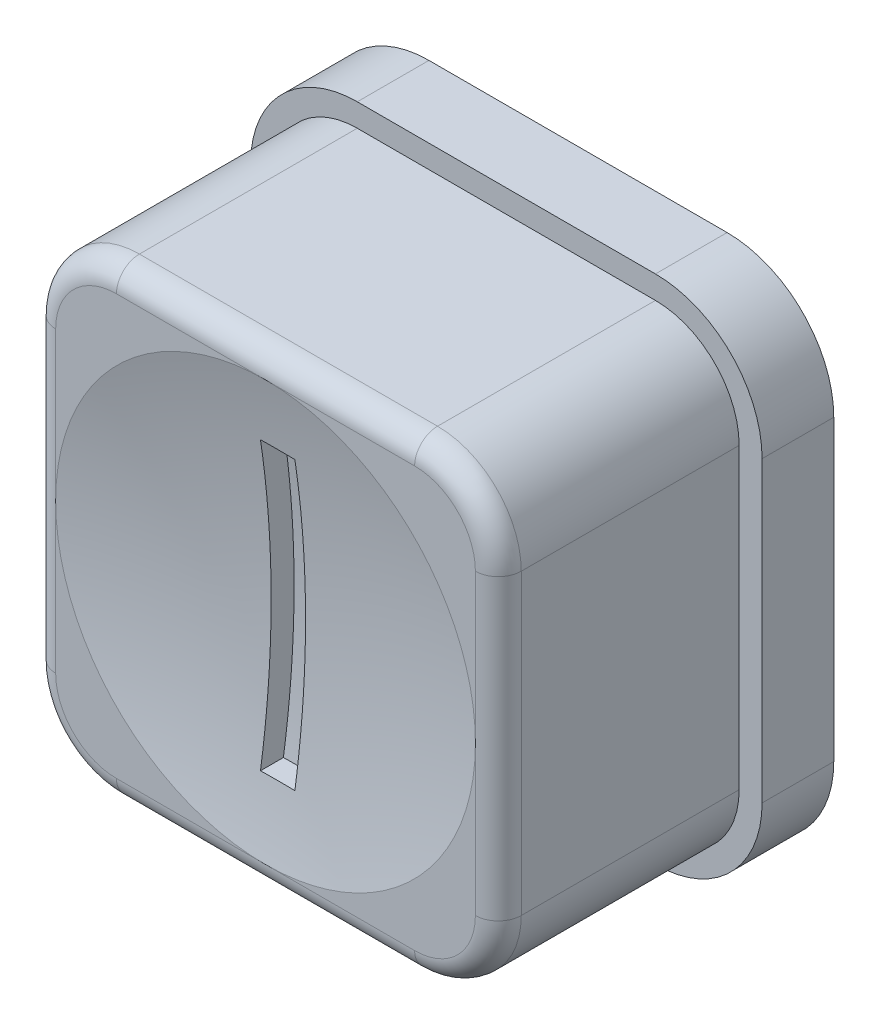
SolidWorks part; units mm, degrees
material "PET"
ref_plane "Front Plane" through (0, 0, 0) normal (0, 0, 1) x (1, 0, 0)
ref_plane "Top Plane" through (0, 0, 0) normal (0, 1, 0) x (1, 0, 0)
ref_plane "Right Plane" through (0, 0, 0) normal (1, 0, 0) x (0, 0, -1)
sketch "Sketch1" plane through (0, 0, 0) normal (0, 0, 1) x (1, 0, 0)
  line L0 (0, 0) -> (-5.1562, 0) construction
  line L4 (0, 5.1562) -> (0, -5.1562) construction
  line L8 (3.302, 5.1562) -> (-3.302, 5.1562)
  line L9 (-5.1562, 3.302) -> (-5.1562, -3.302)
  line L10 (-3.302, -5.1562) -> (3.302, -5.1562)
  line L11 (5.1562, -3.302) -> (5.1562, 3.302)
  arc A8 (-3.302, 5.1562) -> (-5.1562, 3.302) centre (-3.302, 3.302) ccw
  arc A9 (-5.1562, -3.302) -> (-3.302, -5.1562) centre (-3.302, -3.302) ccw
  arc A10 (3.302, -5.1562) -> (5.1562, -3.302) centre (3.302, -3.302) ccw
  arc A11 (5.1562, 3.302) -> (3.302, 5.1562) centre (3.302, 3.302) ccw
  point P6 (0, 0)
  dimension "D3" = 1.8542
  dimension "D4" = 10.3124
  dimension "D1" = 10.3124
  dimension "D5" = 10.3124
extrude "Boss-Extrude1" add sketch "Sketch1" against normal blind 5.334
fillet "Fillet1" radius 0.508 8 edges at (5.1562, 0, 0) (4.6131, -4.6131, 0) (0, -5.1562, 0) (-4.6131, -4.6131, 0) (-5.1562, 0, 0) (-4.6131, 4.6131, 0) (0, 5.1562, 0) (4.6131, 4.6131, 0)
sketch "Sketch2" plane through (0, 0, 0) normal (0, 0, 1) x (1, 0, 0)
  line L0 (0, 0) -> (0, -5.1562) construction
  line L1 (3.302, -5.1562) -> (-3.302, -5.1562) construction
  line L2 (0, 0) -> (5.1562, 0) construction
  line L3 (5.1562, 3.302) -> (5.1562, -3.302) construction
  circle A0 centre (0, 0) radius 4.572
  dimension "D1" = 9.144
extrude "Cut-Extrude1" [suppressed] cut sketch "Sketch2" against normal blind 0.254
sketch "Sketch3" [suppressed] plane through (0, 0, -0.254) normal (0, 0, 1) x (1, 0, 0)
  line L0 (0, -4.572) -> (0, 4.572) construction
  line L1 (-0.254, -4.572) -> (-0.254, 4.572)
  line L2 (0.254, -4.572) -> (0.254, 4.572)
  line L3 (0.254, -4.572) -> (0.254, 4.572)
  circle A0 centre (0, 0) radius 4.572 construction
  circle A1 centre (0, 0) radius 4.572 construction
  arc A2 (-0.254, -4.5649) -> (0.254, -4.5649) centre (0, 0) ccw
  arc A3 (0.254, 4.5649) -> (-0.254, 4.5649) centre (0, 0) ccw
  point P9 (0, 0)
  dimension "D2" = 0.254
  dimension "D1" = 0.254
extrude "Cut-Extrude2" [suppressed] cut sketch "Sketch3" against normal blind 0.127
sketch "Sketch4" plane through (0, 0, -5.334) normal (0, 0, -1) x (-1, 0, 0)
  line L8 (-5.6642, 3.302) -> (-5.6642, -3.302)
  line L9 (-3.302, -5.6642) -> (3.302, -5.6642)
  line L10 (5.6642, -3.302) -> (5.6642, 3.302)
  line L11 (3.302, 5.6642) -> (-3.302, 5.6642)
  line L12 (-5.6642, 3.302) -> (-5.6642, -3.302)
  line L13 (-3.302, -5.6642) -> (3.302, -5.6642)
  line L14 (5.6642, -3.302) -> (5.6642, 3.302)
  line L15 (3.302, 5.6642) -> (-3.302, 5.6642)
  arc A8 (-3.302, 5.6642) -> (-5.6642, 3.302) centre (-3.302, 3.302) ccw
  arc A9 (-5.6642, -3.302) -> (-3.302, -5.6642) centre (-3.302, -3.302) ccw
  arc A10 (3.302, -5.6642) -> (5.6642, -3.302) centre (3.302, -3.302) ccw
  arc A11 (5.6642, 3.302) -> (3.302, 5.6642) centre (3.302, 3.302) ccw
  arc A12 (-3.302, 5.6642) -> (-5.6642, 3.302) centre (-3.302, 3.302) ccw
  arc A13 (-5.6642, -3.302) -> (-3.302, -5.6642) centre (-3.302, -3.302) ccw
  arc A14 (3.302, -5.6642) -> (5.6642, -3.302) centre (3.302, -3.302) ccw
  arc A15 (5.6642, 3.302) -> (3.302, 5.6642) centre (3.302, 3.302) ccw
  dimension "D1" = 0.508
extrude "Boss-Extrude2" add sketch "Sketch4" along normal blind 1.5875
hole_wizard "#56 (0.0465) Diameter Hole1" positions "Sketch6" profile "Sketch7" hole size "#56" standard "ANSI Inch"
sketch "Sketch6" plane through (0, 0, -6.9215) normal (0, 0, -1) x (-1, 0, 0)
  point P0 (0, 0)
sketch "Sketch7" plane through (0, 0, -6.9215) normal (1, 0, 0) x (0, 1, 0)
  line L0 (0, 0) -> (0, 5.08)
  line L1 (0, 5.08) -> (0.5905, 5.08)
  line L2 (0.5905, 5.08) -> (0.5905, 0)
  line L5 (0.5905, 0) -> (0, 0)
  line L10 (0, 5.08) -> (-0.5906, 5.08) construction
  line L11 (0, -6.35) -> (0, 107.95) construction
  dimension "Hole Dia." = 1.1811
  dimension "Hole Depth" = 5.08
  dimension "Drill Angle" = 180
sketch "Sketch8" plane through (0, 0, 0) normal (1, 0, 0) x (0, 0, -1)
  line L0 (0, -3.302) -> (0, 3.302) construction
  line L1 (0.508, 0) -> (0, 0) construction
  line L2 (0, 4.6482) -> (0, 0)
  line L4 (0.508, 0) -> (0, 0)
  arc A0 (0, 4.6482) -> (0.508, 0) centre (-21.0115, 0) cw
  dimension "D1" = 0.508
revolve "Cut-Revolve1" cut sketch "Sketch8" angle 360 about L1
sketch "Sketch9" plane through (0, 0, 0) normal (0, 0, 1) x (1, 0, 0)
  line L1 (0.381, -3.175) -> (-0.381, -3.175)
  line L2 (0.381, -3.175) -> (0.381, 3.175)
  line L3 (0.381, 3.175) -> (-0.381, 3.175)
  line L4 (-0.381, -3.175) -> (-0.381, 3.175)
  line L5 (0.381, -3.175) -> (-0.381, 3.175) construction
  line L6 (0.381, 3.175) -> (-0.381, -3.175) construction
  point P0 (0, 0)
  dimension "D1" = 0.762
  dimension "D2" = 6.35
extrude "Cut-Extrude3" cut sketch "Sketch9" against normal blind 0.508 from surface starting at face at (0, 0, 0)
equation "\"D2@Sketch3\"=\"D1@Sketch3\""
